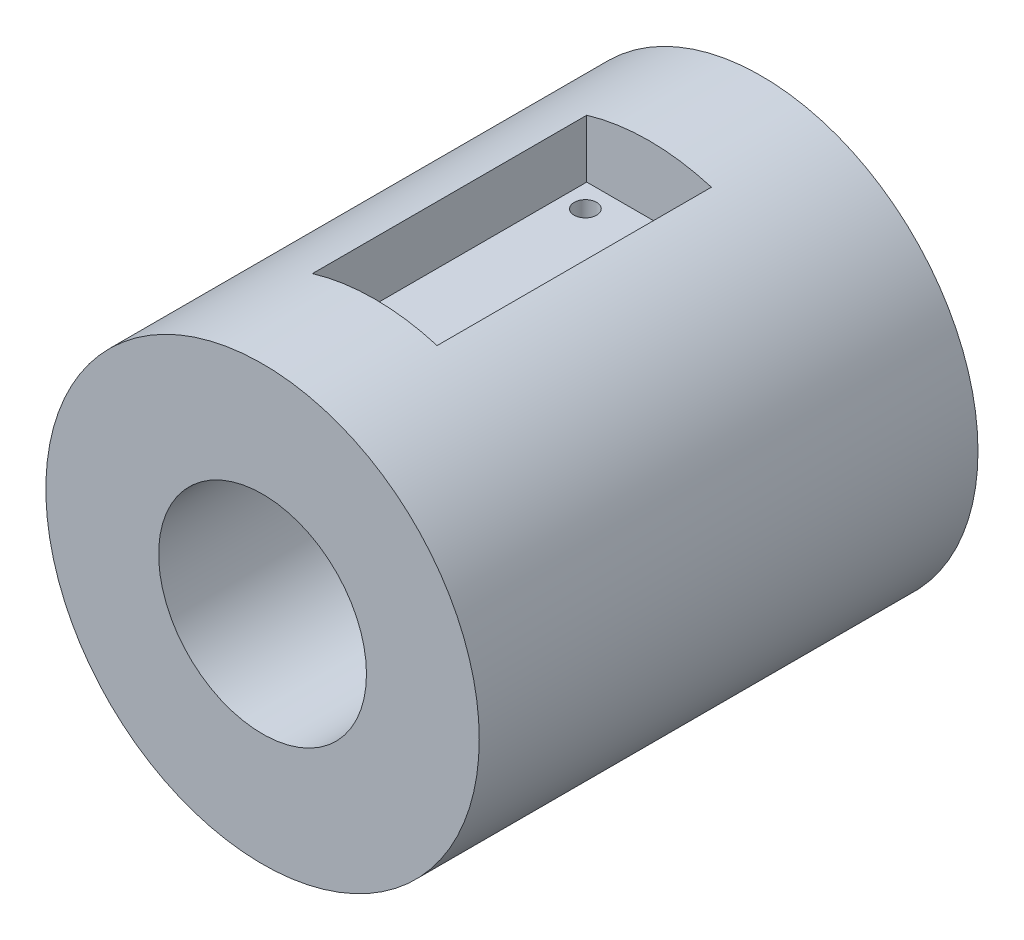
SolidWorks part; units mm, degrees
ref_plane "Front Plane" through (0, 0, 0) normal (0, 0, 1) x (1, 0, 0)
ref_plane "Top Plane" through (0, 0, 0) normal (0, 1, 0) x (1, 0, 0)
ref_plane "Right Plane" through (0, 0, 0) normal (1, 0, 0) x (0, 0, -1)
sketch "ElectronicsBaySketch" plane through (0, 0, 0) normal (0, 0, 1) x (1, 0, 0)
  circle A2 centre (0, 0) radius 43.65 construction
  circle A3 centre (0, 0) radius 43.65 construction
  circle A4 centre (0, 0) radius 43.45
  circle A7 centre (0, 0) radius 20.8375
  circle A8 centre (0, 0) radius 20.6375 construction
  circle A9 centre (0, 0) radius 20.6375 construction
  dimension "D1" = 0.2
  dimension "D2" = 0.2
extrude "ElectronicsBayExtrude" add sketch "ElectronicsBaySketch" along normal blind 100
ref_plane "StratoLoggerPlane" through (0, 30, 0) normal (0, 1, 0) x (1, 0, 0)
sketch "StratoLoggerSketch" plane through (0, 30, 0) normal (0, 1, 0) x (1, 0, 0)
  line L1 (-12.5, -77.5) -> (12.5, -77.5)
  line L2 (-12.5, -77.5) -> (-12.5, -22.5)
  line L3 (-12.5, -22.5) -> (12.5, -22.5)
  line L4 (12.5, -77.5) -> (12.5, -22.5)
  line L5 (-12.5, -77.5) -> (12.5, -22.5) construction
  line L6 (-12.5, -22.5) -> (12.5, -77.5) construction
  point P0 (0, -50)
  point P5 (0, 0)
  dimension "D1" = 55
  dimension "D2" = 25
extrude "StratoLoggerCut" cut sketch "StratoLoggerSketch" along normal through all
sketch "HeatInsertSketch" plane through (0, 30, 0) normal (0, 1, 0) x (1, 0, 0)
  line L0 (-3.3528, -49.8222) -> (-3.3528, -50.2286) construction
  line L1 (-3.3528, -50.2286) -> (3.3528, -50.2286) construction
  line L2 (3.3528, -50.2286) -> (3.3528, -49.8222) construction
  line L3 (3.3528, -35.9538) -> (-3.3528, -35.9538) construction
  line L4 (10.033, -52.9298) -> (5.969, -52.9298)
  line L5 (5.969, -52.9298) -> (5.969, -59.5338)
  line L6 (5.969, -59.5338) -> (10.033, -59.5338)
  line L7 (10.033, -59.5338) -> (10.033, -52.9298)
  line L8 (10.033, -52.9298) -> (5.969, -52.9298) construction
  line L9 (5.969, -52.9298) -> (5.969, -59.5338) construction
  line L10 (5.969, -59.5338) -> (10.033, -59.5338) construction
  line L11 (10.033, -59.5338) -> (10.033, -52.9298) construction
  line L12 (-10.414, -49.746) -> (-3.429, -49.746)
  line L13 (-3.429, -49.746) -> (-3.429, -35.776)
  line L14 (-3.429, -35.776) -> (-10.414, -35.776)
  line L15 (-10.414, -35.776) -> (-10.414, -49.746)
  line L16 (-10.414, -49.746) -> (-3.429, -49.746) construction
  line L17 (-3.429, -49.746) -> (-3.429, -35.776) construction
  line L18 (-3.429, -35.776) -> (-10.414, -35.776) construction
  line L19 (-10.414, -35.776) -> (-10.414, -49.746) construction
  line L20 (3.429, -49.746) -> (10.414, -49.746)
  line L21 (3.429, -35.776) -> (3.429, -49.746)
  line L22 (10.414, -35.776) -> (3.429, -35.776)
  line L23 (10.414, -49.746) -> (10.414, -35.776)
  line L24 (3.429, -49.746) -> (10.414, -49.746) construction
  line L25 (3.429, -35.776) -> (3.429, -49.746) construction
  line L26 (10.414, -35.776) -> (3.429, -35.776) construction
  line L27 (10.414, -49.746) -> (10.414, -35.776) construction
  line L28 (3.3528, -49.8222) -> (10.4902, -49.8222)
  line L29 (10.4902, -49.8222) -> (10.4902, -35.6998)
  line L30 (10.4902, -35.6998) -> (3.3528, -35.6998)
  line L31 (3.3528, -35.6998) -> (3.3528, -49.8222)
  line L32 (3.3528, -49.8222) -> (10.4902, -49.8222) construction
  line L33 (10.4902, -49.8222) -> (10.4902, -35.6998) construction
  line L34 (10.4902, -35.6998) -> (3.3528, -35.6998) construction
  line L35 (3.3528, -35.6998) -> (3.3528, -49.8222) construction
  line L36 (5.8928, -59.61) -> (10.1092, -59.61)
  line L37 (10.1092, -59.61) -> (10.1092, -52.8536)
  line L38 (10.1092, -52.8536) -> (5.8928, -52.8536)
  line L39 (5.8928, -52.8536) -> (5.8928, -59.61)
  line L40 (5.8928, -59.61) -> (10.1092, -59.61) construction
  line L41 (10.1092, -59.61) -> (10.1092, -52.8536) construction
  line L42 (10.1092, -52.8536) -> (5.8928, -52.8536) construction
  line L43 (5.8928, -52.8536) -> (5.8928, -59.61) construction
  line L44 (-2.7432, -73.6474) -> (2.7432, -73.6474)
  line L45 (2.7432, -73.6474) -> (2.7432, -70.828)
  line L46 (2.7432, -70.828) -> (-2.7432, -70.828)
  line L47 (-2.7432, -70.828) -> (-2.7432, -73.6474)
  line L48 (-2.7432, -73.6474) -> (2.7432, -73.6474) construction
  line L49 (2.7432, -73.6474) -> (2.7432, -70.828) construction
  line L50 (2.7432, -70.828) -> (-2.7432, -70.828) construction
  line L51 (-2.7432, -70.828) -> (-2.7432, -73.6474) construction
  line L52 (-10.4902, -49.8222) -> (-3.3528, -49.8222)
  line L53 (-10.4902, -35.6998) -> (-10.4902, -49.8222)
  line L54 (-3.3528, -35.6998) -> (-10.4902, -35.6998)
  line L55 (-3.3528, -49.8222) -> (-3.3528, -35.6998)
  line L56 (-10.4902, -49.8222) -> (-3.3528, -49.8222) construction
  line L57 (-10.4902, -35.6998) -> (-10.4902, -49.8222) construction
  line L58 (-3.3528, -35.6998) -> (-10.4902, -35.6998) construction
  line L59 (-3.3528, -49.8222) -> (-3.3528, -35.6998) construction
  line L60 (2.8194, -70.7518) -> (-2.8194, -70.7518)
  line L61 (2.8194, -73.7236) -> (2.8194, -70.7518)
  line L62 (-2.8194, -73.7236) -> (2.8194, -73.7236)
  line L63 (-2.8194, -70.7518) -> (-2.8194, -73.7236)
  line L64 (2.8194, -70.7518) -> (-2.8194, -70.7518) construction
  line L65 (2.8194, -73.7236) -> (2.8194, -70.7518) construction
  line L66 (-2.8194, -73.7236) -> (2.8194, -73.7236) construction
  line L67 (-2.8194, -70.7518) -> (-2.8194, -73.7236) construction
  line L68 (-1.143, -72.7457) -> (1.143, -72.7457)
  line L69 (-1.143, -71.7297) -> (-1.143, -72.7457)
  line L70 (1.143, -71.7297) -> (-1.143, -71.7297)
  line L71 (1.143, -72.7457) -> (1.143, -71.7297)
  line L72 (-1.143, -72.7457) -> (1.143, -72.7457) construction
  line L73 (-1.143, -71.7297) -> (-1.143, -72.7457) construction
  line L74 (1.143, -71.7297) -> (-1.143, -71.7297) construction
  line L75 (1.143, -72.7457) -> (1.143, -71.7297) construction
  line L76 (-7.0485, -53.1076) -> (-9.8425, -53.1076)
  line L77 (-7.0485, -58.6956) -> (-7.0485, -53.1076)
  line L78 (-9.8425, -58.6956) -> (-7.0485, -58.6956)
  line L79 (-9.8425, -53.1076) -> (-9.8425, -58.6956)
  line L80 (-7.0485, -53.1076) -> (-9.8425, -53.1076) construction
  line L81 (-7.0485, -58.6956) -> (-7.0485, -53.1076) construction
  line L82 (-9.8425, -58.6956) -> (-7.0485, -58.6956) construction
  line L83 (-9.8425, -53.1076) -> (-9.8425, -58.6956) construction
  line L84 (-6.7818, -52.8282) -> (-10.1092, -52.8282)
  line L85 (-6.7818, -58.975) -> (-6.7818, -52.8282)
  line L86 (-10.1092, -58.975) -> (-6.7818, -58.975)
  line L87 (-10.1092, -52.8282) -> (-10.1092, -58.975)
  line L88 (-6.7818, -52.8282) -> (-10.1092, -52.8282) construction
  line L89 (-6.7818, -58.975) -> (-6.7818, -52.8282) construction
  line L90 (-10.1092, -58.975) -> (-6.7818, -58.975) construction
  line L91 (-10.1092, -52.8282) -> (-10.1092, -58.975) construction
  line L92 (-6.858, -52.9044) -> (-10.033, -52.9044)
  line L93 (-6.858, -58.8988) -> (-6.858, -52.9044)
  line L94 (-10.033, -58.8988) -> (-6.858, -58.8988)
  line L95 (-10.033, -52.9044) -> (-10.033, -58.8988)
  line L96 (-6.858, -52.9044) -> (-10.033, -52.9044) construction
  line L97 (-6.858, -58.8988) -> (-6.858, -52.9044) construction
  line L98 (-10.033, -58.8988) -> (-6.858, -58.8988) construction
  line L99 (-10.033, -52.9044) -> (-10.033, -58.8988) construction
  line L100 (-7.9756, -53.8823) -> (-7.5946, -53.8823)
  line L101 (-7.5946, -53.8823) -> (-7.5946, -53.8569)
  line L102 (-7.5946, -53.8569) -> (-7.9756, -53.8569)
  line L103 (-7.9756, -53.8569) -> (-7.9756, -53.8823)
  line L104 (-7.9756, -53.8823) -> (-7.5946, -53.8823) construction
  line L105 (-7.5946, -53.8823) -> (-7.5946, -53.8569) construction
  line L106 (-7.5946, -53.8569) -> (-7.9756, -53.8569) construction
  line L107 (-7.9756, -53.8569) -> (-7.9756, -53.8823) construction
  line L108 (-7.5946, -55.8889) -> (-7.9756, -55.8889)
  line L109 (-7.5946, -55.9143) -> (-7.5946, -55.8889)
  line L110 (-7.9756, -55.9143) -> (-7.5946, -55.9143)
  line L111 (-7.9756, -55.8889) -> (-7.9756, -55.9143)
  line L112 (-7.5946, -55.8889) -> (-7.9756, -55.8889) construction
  line L113 (-7.5946, -55.9143) -> (-7.5946, -55.8889) construction
  line L114 (-7.9756, -55.9143) -> (-7.5946, -55.9143) construction
  line L115 (-7.9756, -55.8889) -> (-7.9756, -55.9143) construction
  line L116 (-7.9756, -54.8983) -> (-7.5946, -54.8983)
  line L117 (-7.5946, -54.8983) -> (-7.5946, -54.8729)
  line L118 (-7.5946, -54.8729) -> (-7.9756, -54.8729)
  line L119 (-7.9756, -54.8729) -> (-7.9756, -54.8983)
  line L120 (-7.9756, -54.8983) -> (-7.5946, -54.8983) construction
  line L121 (-7.5946, -54.8983) -> (-7.5946, -54.8729) construction
  line L122 (-7.5946, -54.8729) -> (-7.9756, -54.8729) construction
  line L123 (-7.9756, -54.8729) -> (-7.9756, -54.8983) construction
  line L124 (3.2766, -36.03) -> (-3.2766, -36.03)
  line L125 (-3.2766, -36.03) -> (-3.2766, -50.1524)
  line L126 (-3.2766, -50.1524) -> (3.2766, -50.1524)
  line L127 (3.2766, -50.1524) -> (3.2766, -36.03)
  line L128 (3.2766, -36.03) -> (-3.2766, -36.03) construction
  line L129 (-3.2766, -36.03) -> (-3.2766, -50.1524) construction
  line L130 (-3.2766, -50.1524) -> (3.2766, -50.1524) construction
  line L131 (3.2766, -50.1524) -> (3.2766, -36.03) construction
  line L132 (-7.9756, -57.9463) -> (-7.5946, -57.9463)
  line L133 (-7.5946, -57.9463) -> (-7.5946, -57.9209)
  line L134 (-7.5946, -57.9209) -> (-7.9756, -57.9209)
  line L135 (-7.9756, -57.9209) -> (-7.9756, -57.9463)
  line L136 (-7.9756, -57.9463) -> (-7.5946, -57.9463) construction
  line L137 (-7.5946, -57.9463) -> (-7.5946, -57.9209) construction
  line L138 (-7.5946, -57.9209) -> (-7.9756, -57.9209) construction
  line L139 (-7.9756, -57.9209) -> (-7.9756, -57.9463) construction
  line L140 (-7.5946, -56.9303) -> (-7.5946, -56.9049)
  line L141 (-7.9756, -56.9303) -> (-7.5946, -56.9303)
  line L142 (-7.9756, -56.9049) -> (-7.9756, -56.9303)
  line L143 (-7.5946, -56.9049) -> (-7.9756, -56.9049)
  line L144 (-7.5946, -56.9303) -> (-7.5946, -56.9049) construction
  line L145 (-7.9756, -56.9303) -> (-7.5946, -56.9303) construction
  line L146 (-7.9756, -56.9049) -> (-7.9756, -56.9303) construction
  line L147 (-7.5946, -56.9049) -> (-7.9756, -56.9049) construction
  line L148 (10.668, -24.6) -> (-10.668, -24.6)
  line L149 (10.668, -75.4) -> (10.668, -24.6)
  line L150 (-10.668, -75.4) -> (10.668, -75.4)
  line L151 (-10.668, -24.6) -> (-10.668, -75.4)
  line L152 (10.668, -24.6) -> (-10.668, -24.6) construction
  line L153 (10.668, -75.4) -> (10.668, -24.6) construction
  line L154 (-10.668, -75.4) -> (10.668, -75.4) construction
  line L155 (-10.668, -24.6) -> (-10.668, -75.4) construction
  line L156 (-3.3528, -49.8222) -> (-3.3528, -50.2286) construction
  line L157 (-3.3528, -50.2286) -> (3.3528, -50.2286) construction
  line L158 (3.3528, -50.2286) -> (3.3528, -49.8222) construction
  line L159 (3.3528, -35.9538) -> (-3.3528, -35.9538) construction
  circle A0 centre (-8.001, -27.267) radius 2.25
  circle A1 centre (-8.001, -72.733) radius 2.032
  circle A2 centre (-8.001, -72.733) radius 2.032 construction
  circle A3 centre (8.001, -72.733) radius 2.032
  circle A4 centre (8.001, -72.733) radius 2.032 construction
  circle A5 centre (8.001, -27.267) radius 2.032
  circle A6 centre (8.001, -27.267) radius 2.032 construction
  circle A7 centre (-8.001, -27.267) radius 2.032
  circle A8 centre (-8.001, -27.267) radius 2.032 construction
  circle A9 centre (0, -30.5055) radius 5.2705
  circle A10 centre (0, -30.5055) radius 5.2705 construction
  circle A11 centre (8.509, -58.0098) radius 0.254
  circle A12 centre (8.509, -58.0098) radius 0.254 construction
  circle A13 centre (-8.001, -27.267) radius 1.3716
  circle A14 centre (-8.001, -27.267) radius 1.3716 construction
  circle A15 centre (8.001, -27.267) radius 1.3716
  circle A16 centre (8.001, -27.267) radius 1.3716 construction
  circle A17 centre (8.001, -72.733) radius 1.3716
  circle A18 centre (8.001, -72.733) radius 1.3716 construction
  circle A19 centre (-8.001, -72.733) radius 1.3716
  circle A20 centre (-8.001, -72.733) radius 1.3716 construction
  circle A21 centre (8.509, -58.0098) radius 0.635
  circle A22 centre (8.509, -58.0098) radius 0.635 construction
  circle A23 centre (8.509, -56.2318) radius 0.635
  circle A24 centre (8.509, -56.2318) radius 0.635 construction
  circle A25 centre (8.509, -54.4538) radius 0.635
  circle A26 centre (8.509, -54.4538) radius 0.635 construction
  circle A27 centre (8.509, -54.4538) radius 0.254
  circle A28 centre (8.509, -54.4538) radius 0.254 construction
  circle A29 centre (8.509, -56.2318) radius 0.254
  circle A30 centre (8.509, -56.2318) radius 0.254 construction
  circle A31 centre (0, -30.5055) radius 5.3467
  circle A32 centre (0, -30.5055) radius 5.3467 construction
  circle A33 centre (0, -30.5055) radius 0.762
  circle A34 centre (0, -30.5055) radius 0.762 construction
  circle A35 centre (8.001, -27.267) radius 2.25
  circle A36 centre (8.001, -72.733) radius 2.25
  circle A37 centre (-8.001, -72.733) radius 2.25
  dimension "D37" = 4.5
  dimension "D1" = 0
  dimension "D2" = 0
  dimension "D3" = 0
  dimension "D4" = 0
  dimension "D5" = 0
  dimension "D6" = 0
  dimension "D7" = 0
  dimension "D8" = 0
  dimension "D9" = 0
  dimension "D10" = 0
  dimension "D11" = 0
  dimension "D12" = 0
  dimension "D13" = 0
  dimension "D14" = 0
  dimension "D15" = 0
  dimension "D16" = 0
  dimension "D17" = 0
  dimension "D18" = 0
  dimension "D19" = 0
  dimension "D20" = 0
  dimension "D21" = 0
  dimension "D22" = 0
  dimension "D23" = 0
  dimension "D24" = 0
  dimension "D25" = 0
  dimension "D26" = 0
  dimension "D27" = 0
  dimension "D28" = 0
  dimension "D29" = 0
  dimension "D30" = 0
  dimension "D31" = 0
  dimension "D32" = 0
  dimension "D33" = 0
  dimension "D34" = 0
  dimension "D35" = 0
  dimension "D36" = 0
extrude "Cut-Extrude2" cut sketch "HeatInsertSketch" against normal blind 6
